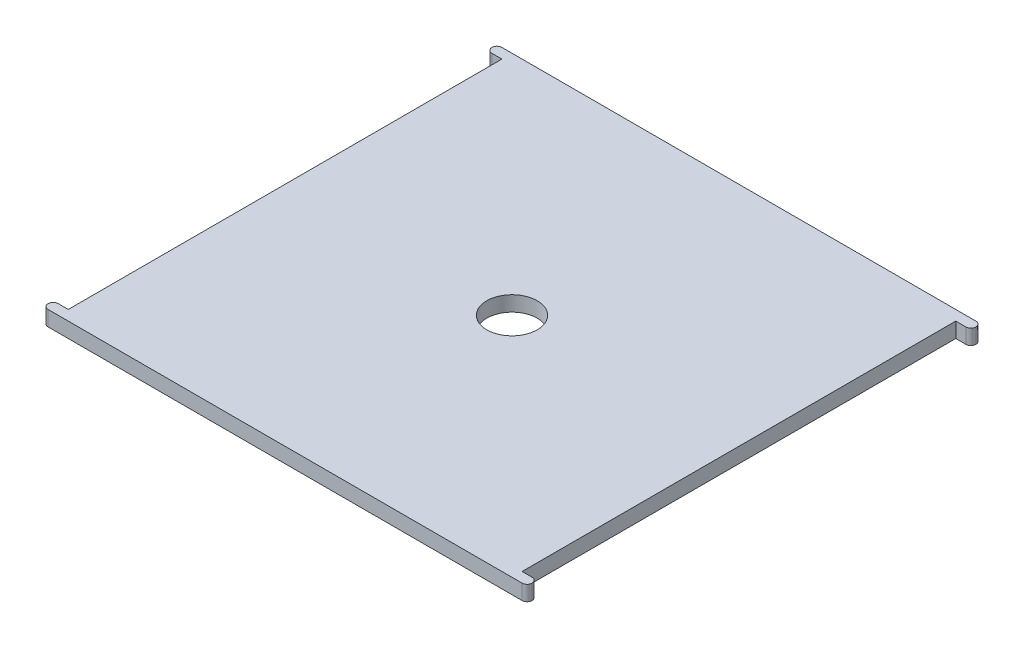
SolidWorks part; units mm, degrees
ref_plane "Front Plane" through (0, 0, 0) normal (0, 0, 1) x (1, 0, 0)
ref_plane "Top Plane" through (0, 0, 0) normal (0, 1, 0) x (1, 0, 0)
ref_plane "Right Plane" through (0, 0, 0) normal (1, 0, 0) x (0, 0, -1)
sketch "Sketch1" plane through (0, 0, 0) normal (0, 1, 0) x (1, 0, 0)
  line L0 (-71.4375, 65.0875) -> (71.4375, 65.0875) construction
  line L1 (-71.4375, -71.4375) -> (71.4375, -71.4375)
  line L2 (-71.4375, -68.2625) -> (-71.4375, 68.2625)
  line L3 (-71.4375, 71.4375) -> (71.4375, 71.4375)
  line L4 (71.4375, -68.2625) -> (71.4375, 68.2625)
  line L5 (-71.4375, -71.4375) -> (71.4375, 71.4375) construction
  line L6 (-71.4375, 71.4375) -> (71.4375, -71.4375) construction
  line L7 (-71.4375, 68.2625) -> (71.4375, 68.2625) construction
  line L8 (-71.4375, -68.2625) -> (71.4375, -68.2625) construction
  line L9 (-71.4375, 71.4375) -> (-76.2, 71.4375)
  line L11 (-71.4375, 68.2625) -> (-76.2, 68.2625)
  line L12 (-76.2, 71.4375) -> (-76.2, 68.2625)
  line L13 (71.4375, 71.4375) -> (76.2, 71.4375)
  line L14 (-71.4375, -68.2625) -> (-76.2, -68.2625)
  line L15 (71.4375, 68.2625) -> (76.2, 68.2625)
  line L16 (76.2, 71.4375) -> (76.2, 68.2625)
  line L18 (-71.4375, -71.4375) -> (-76.2, -71.4375)
  line L19 (-76.2, -68.2625) -> (-76.2, -71.4375)
  line L20 (71.4375, -68.2625) -> (76.2, -68.2625)
  line L22 (71.4375, -71.4375) -> (76.2, -71.4375)
  line L23 (76.2, -68.2625) -> (76.2, -71.4375)
  point P0 (0, 0)
  dimension "D1" = 142.875
  dimension "D2" = 6.35
  dimension "D3" = 3.175
  dimension "D4" = 4.7625
  dimension "D5" = 4.7625
  dimension "D6" = 3.175
  dimension "D7" = 4.7625
  dimension "D8" = 4.7625
extrude "Boss-Extrude1" add sketch "Sketch1" along normal blind 4.7625
hole_wizard "5/8 (0.625) Diameter Hole1" positions "Sketch2" profile "Sketch3" hole size "5/8" standard "ANSI Inch" end condition through all
sketch "Sketch2" plane through (0, 4.7625, 0) normal (0, 1, 0) x (1, 0, 0)
  line L7 (-76.2, 71.4375) -> (76.2, -71.4375) construction
  point P44 (0, 0)
sketch "Sketch3" plane through (0, 4.7625, 0) normal (1, 0, 0) x (0, 0, 1)
  line L0 (0, 0) -> (0, 4.7625)
  line L1 (0, 4.7625) -> (7.9375, 4.7625)
  line L2 (7.9375, 4.7625) -> (7.9375, 0)
  line L5 (7.9375, 0) -> (0, 0)
  line L11 (0, -6.35) -> (0, 107.95) construction
  dimension "Thru Hole Dia." = 15.875
  dimension "Thru Hole Depth" = 4.7625
fillet "Fillet1" radius 1.5875 8 edges at (-76.2, 2.3813, 71.4375) (-76.2, 2.3813, 68.2625) (76.2, 2.3813, 71.4375) (76.2, 2.3813, 68.2625) (76.2, 2.3813, -68.2625) (76.2, 2.3813, -71.4375) (-76.2, 2.3813, -68.2625) (-76.2, 2.3813, -71.4375)
